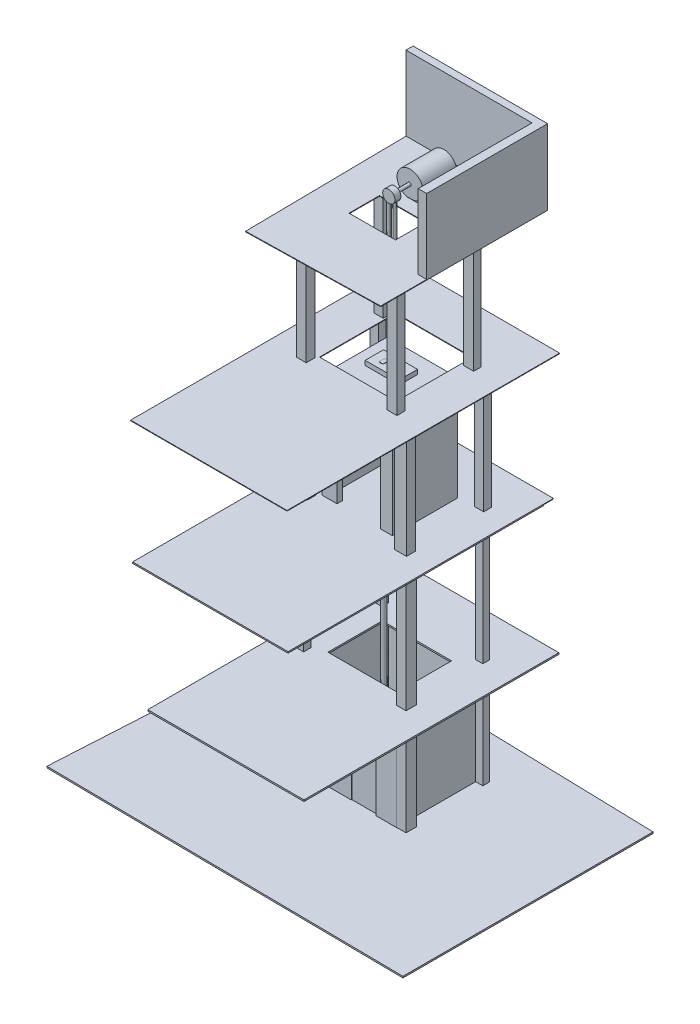
SolidWorks part; units mm, degrees
ref_plane "Front Plane" through (0, 0, 0) normal (0, 0, 1) x (1, 0, 0)
ref_plane "Top Plane" through (0, 0, 0) normal (0, 1, 0) x (1, 0, 0)
ref_plane "Right Plane" through (0, 0, 0) normal (1, 0, 0) x (0, 0, -1)
sketch "Sketch1" plane through (0, 0, 0) normal (0, 1, 0) x (1, 0, 0)
  line L1 (-1119.5185, 584.2256) -> (1199.1194, 522.7665)
  line L2 (-1119.5185, 584.2256) -> (-1218.0451, -1131.0237)
  line L3 (-1218.0451, -1131.0237) -> (1199.1194, -1157.1766)
  line L4 (1199.1194, 522.7665) -> (1199.1194, -1157.1766)
  line L5 (-1119.5185, 584.2256) -> (1199.1194, -1157.1766) construction
  line L6 (-1218.0451, -1131.0237) -> (1199.1194, 522.7665) construction
  point P0 (0, 0)
extrude "Boss-Extrude1" add sketch "Sketch1" along normal blind 10
sketch "Sketch2" plane through (0, 10, 0) normal (0, 1, 0) x (1, 0, 0)
  line L1 (-310.9875, 262.3228) -> (311.3377, 262.3228)
  line L2 (-310.9875, 262.3228) -> (-310.9875, -313.9536)
  line L3 (-310.9875, -313.9536) -> (311.3377, -313.9536)
  line L4 (311.3377, 262.3228) -> (311.3377, -313.9536)
  line L5 (-272.0145, 218.0111) -> (278.8911, 218.0111)
  line L6 (-272.0145, 218.0111) -> (-272.0145, -277.642)
  line L7 (-272.0145, -277.642) -> (278.8911, -277.642)
  line L8 (278.8911, 218.0111) -> (278.8911, -277.642)
extrude "Boss-Extrude2" add sketch "Sketch2" along normal blind 700
sketch "Sketch3" plane through (0, 710, 0) normal (0, 1, 0) x (1, 0, 0)
  line L1 (-498.5759, 538.5603) -> (550.6847, 538.5603)
  line L2 (-498.5759, 538.5603) -> (-498.5759, -1173.1855)
  line L3 (-498.5759, -1173.1855) -> (550.6847, -1173.441)
  line L4 (550.6847, 538.5603) -> (550.6847, -1173.441)
extrude "Boss-Extrude3" add sketch "Sketch3" along normal blind 10
sketch "Sketch4" plane through (0, 0, 313.9536) normal (0, 0, 1) x (1, 0, 0)
  line L1 (-169.9016, 641.4575) -> (173.8441, 641.4575)
  line L2 (-169.9016, 641.4575) -> (-169.9016, 10)
  line L3 (-169.9016, 10) -> (173.8441, 10)
  line L4 (173.8441, 641.4575) -> (173.8441, 10)
extrude "Cut-Extrude1" cut sketch "Sketch4" against normal blind 40
sketch "Sketch5" plane through (0, 0, 313.9536) normal (0, 0, 1) x (1, 0, 0)
  line L1 (-283.6713, 474.5331) -> (-187.5856, 474.5331)
  line L2 (-283.6713, 474.5331) -> (-283.6713, 265.4455)
  line L3 (-283.6713, 265.4455) -> (-187.5856, 265.4455)
  line L4 (-187.5856, 474.5331) -> (-187.5856, 265.4455)
extrude "Boss-Extrude4" add sketch "Sketch5" along normal blind 1
sketch "Sketch6" plane through (0, 0, 314.9536) normal (0, 0, 1) x (1, 0, 0)
  line L1 (-271.1746, 418.75) -> (-195.647, 418.75)
  line L2 (-271.1746, 418.75) -> (-271.1746, 375.0617)
  line L3 (-271.1746, 375.0617) -> (-195.647, 375.0617)
  line L4 (-195.647, 418.75) -> (-195.647, 375.0617)
extrude "Cut-Extrude2" cut sketch "Sketch6" against normal blind 1
sketch "Sketch7" plane through (0, 0, 314.9536) normal (0, 0, 1) x (1, 0, 0)
  circle A0 centre (-236.0757, 343.6172) radius 20.2971
  circle A1 centre (-236.0757, 291.5015) radius 20.232
extrude "Boss-Extrude5" add sketch "Sketch7" along normal blind 1
sketch "Sketch8" plane through (0, 0, 315.9536) normal (0, 0, 1) x (1, 0, 0)
  line L0 (-248.1005, 334.3432) -> (-224.1168, 334.3432)
  line L1 (-224.1168, 334.3432) -> (-236.1087, 356.5701)
  line L2 (-236.1087, 356.5701) -> (-248.1005, 334.3432)
  line L3 (-248.1005, 300.7341) -> (-224.1168, 300.7341)
  line L4 (-224.1168, 300.7341) -> (-236.1087, 278.0211)
  line L5 (-236.1087, 278.0211) -> (-248.1005, 300.7341)
extrude "Boss-Extrude6" add sketch "Sketch8" along normal blind 1
sketch "Sketch9" plane through (-169.9016, 0, 0) normal (1, 0, 0) x (0, 0, -1)
  line L1 (-304.9322, 641.4575) -> (-277.642, 641.4575)
  line L2 (-304.9322, 641.4575) -> (-304.9322, 10)
  line L3 (-304.9322, 10) -> (-277.642, 10)
  line L4 (-277.642, 641.4575) -> (-277.642, 10)
extrude "Boss-Extrude7" add sketch "Sketch9" along normal blind 170
sketch "Sketch10" plane through (0.0984, 0, 0) normal (1, 0, 0) x (0, 0, -1)
  line L1 (-301.4683, 640.5034) -> (-277.642, 640.5034)
  line L2 (-301.4683, 640.5034) -> (-301.4683, 10)
  line L3 (-301.4683, 10) -> (-277.642, 10)
  line L4 (-277.642, 640.5034) -> (-277.642, 10)
extrude "Boss-Extrude8" add sketch "Sketch10" along normal blind 170
sketch "Sketch11" plane through (0, 0, 313.9536) normal (0, 0, 1) x (1, 0, 0)
  line L1 (-53.7077, 693.9278) -> (48.7244, 693.9278)
  line L2 (-53.7077, 693.9278) -> (-53.7077, 651.2448)
  line L3 (-53.7077, 651.2448) -> (48.7244, 651.2448)
  line L4 (48.7244, 693.9278) -> (48.7244, 651.2448)
extrude "Boss-Extrude9" add sketch "Sketch11" along normal blind 1
sketch "Sketch12" plane through (0, 0, 314.9536) normal (0, 0, 1) x (1, 0, 0)
  line L1 (-47.5467, 689.1219) -> (41.8868, 689.1219)
  line L2 (-47.5467, 689.1219) -> (-47.5467, 655.2159)
  line L3 (-47.5467, 655.2159) -> (41.8868, 655.2159)
  line L4 (41.8868, 689.1219) -> (41.8868, 655.2159)
extrude "Cut-Extrude3" cut sketch "Sketch12" against normal blind 1
sketch "Sketch13" plane through (0, 0, 313.9536) normal (0, 0, 1) x (1, 0, 0)
  line L0 (-16.1887, 682.3335) -> (-12.3636, 682.3335)
  line L1 (-12.3636, 682.3335) -> (-16.2809, 666.1802)
  line L2 (-16.2809, 666.1802) -> (-10.8261, 666.1802)
  line L3 (-5.3714, 666.1802) -> (-5.3714, 662.7972)
  line L4 (-5.3714, 662.7972) -> (-7.9099, 662.7972)
  line L5 (-21.2894, 662.7972) -> (-16.1887, 682.3335)
  line L6 (-10.8261, 671.5233) -> (-10.8261, 666.1802)
  line L7 (-10.8261, 659.937) -> (-7.9099, 659.937)
  line L8 (-7.9099, 659.937) -> (-7.9099, 662.7972)
  line L9 (-7.9099, 671.5233) -> (-10.8261, 671.5233)
  line L10 (-10.8261, 662.7972) -> (-10.8261, 659.937)
  line L11 (-7.9099, 666.1802) -> (-5.3714, 666.1802)
  line L12 (-7.9099, 666.1802) -> (-7.9099, 671.5233)
  line L13 (-10.8261, 662.7972) -> (-21.2894, 662.7972)
extrude "Boss-Extrude10" add sketch "Sketch13" along normal blind 1
sketch "Sketch14" plane through (0, 0, 313.9536) normal (0, 0, 1) x (1, 0, 0)
  line L0 (8.2825, 678.5261) -> (25.4536, 678.5261)
  line L1 (25.4536, 678.5261) -> (16.868, 660.4022)
  line L2 (16.868, 660.4022) -> (8.2825, 678.5261)
extrude "Boss-Extrude11" add sketch "Sketch14" along normal blind 1
sketch "Sketch15" plane through (0, 0, 313.9536) normal (0, 0, 1) x (1, 0, 0)
  line L0 (-253.3924, 406.4083) -> (-253.3924, 387.5651)
  line L1 (-253.3924, 387.5651) -> (-258.9323, 387.5651)
  line L2 (-258.9323, 387.5651) -> (-258.9323, 385.0304)
  line L3 (-258.9323, 385.0304) -> (-244.3761, 385.0304)
  line L4 (-244.3761, 385.0304) -> (-244.3761, 387.5681)
  line L5 (-244.3761, 387.5681) -> (-249.8802, 387.5681)
  line L6 (-249.8802, 387.5681) -> (-249.8802, 410.5631)
  line L7 (-249.8802, 410.5631) -> (-259.6929, 410.2522)
  line L8 (-259.6929, 410.2522) -> (-259.5666, 406.4083)
  line L9 (-259.5666, 406.4083) -> (-253.3924, 406.4083)
extrude "Boss-Extrude12" add sketch "Sketch15" along normal blind 1
sketch "Sketch16" plane through (0, 0, 313.9536) normal (0, 0, 1) x (1, 0, 0)
  line L0 (-235.6485, 408.4658) -> (-235.6485, 385.5858)
  line L1 (-235.6485, 385.5858) -> (-232.1063, 385.5858)
  line L2 (-232.1063, 385.5858) -> (-232.2231, 401.9914)
  line L3 (-235.6485, 408.4658) -> (-231.8951, 408.4658)
  line L4 (-231.8951, 408.4658) -> (-231.8951, 406.5499)
  line L5 (-221.9834, 403.0568) -> (-221.9834, 385.5858)
  line L6 (-221.9834, 385.5858) -> (-218.8212, 385.5858)
  line L7 (-218.8212, 385.5858) -> (-219.0863, 397.9701)
  line L8 (-208.8863, 401.5917) -> (-208.8863, 385.5858)
  line L9 (-208.8863, 385.5858) -> (-206.271, 385.5858)
  line L10 (-206.271, 385.5858) -> (-206.5126, 401.9271)
  line L11 (-219.2828, 403.1887) -> (-219.0863, 397.9701)
  arc A4 (-221.9834, 403.0568) -> (-232.2231, 401.9914) centre (-226.8379, 399.9737) ccw
  arc A6 (-208.8863, 401.5917) -> (-219.2828, 403.1887) centre (-214.4049, 400.3049) ccw
  arc A7 (-206.5126, 401.9271) -> (-220.6047, 405.4509) centre (-214.4049, 400.3049) ccw
  arc A8 (-220.6047, 405.4509) -> (-231.8951, 406.6078) centre (-226.8379, 400.2912) ccw
  line M5 (-271.1746, 418.75) -> (-271.1746, 375.0617)
  line M6 (-271.1746, 375.0617) -> (-195.647, 375.0617)
  line M7 (-195.647, 375.0617) -> (-195.647, 418.75)
  line M8 (-195.647, 418.75) -> (-271.1746, 418.75)
  line M9 (-253.3924, 387.5651) -> (-253.3924, 406.4083)
  line M10 (-253.3924, 406.4083) -> (-259.5666, 406.4083)
  line M11 (-259.5666, 406.4083) -> (-259.6929, 410.2522)
  line M12 (-259.6929, 410.2522) -> (-249.8802, 410.5631)
  line M13 (-249.8802, 410.5631) -> (-249.8802, 387.5681)
  line M14 (-249.8802, 387.5681) -> (-244.3761, 387.5681)
  line M15 (-244.3761, 387.5681) -> (-244.3761, 385.0304)
  line M16 (-244.3761, 385.0304) -> (-258.9323, 385.0304)
  line M17 (-258.9323, 385.0304) -> (-258.9323, 387.5651)
  line M18 (-258.9323, 387.5651) -> (-253.3924, 387.5651)
extrude "Cut-Extrude4" cut sketch "Sketch16" against normal blind 2 contours A8 A7 L10 L9 L8 A6 L11 L7 L6 L5 A4 L2 L1 L0 L3 L4 M8 M5 M6 M7 M18 M9 M10 M11 M12 M13 M14 M15 M16 M17 region at (-233.4108, 417.8775, 313.9536)
sketch "Sketch17" plane through (0, 0, 311.9536) normal (0, 0, 1) x (1, 0, 0)
  line L1 (-271.2094, 458.8572) -> (-195.647, 458.8572)
  line L2 (-271.2094, 458.8572) -> (-271.2094, 418.4414)
  line L3 (-271.2094, 418.4414) -> (-195.7041, 418.4414)
  line L4 (-195.647, 458.8572) -> (-195.7041, 418.4414)
extrude "Cut-Extrude5" cut sketch "Sketch17" against normal blind 1
sketch "Sketch18" plane through (0, 0, 314.9536) normal (0, 0, 1) x (1, 0, 0)
  line L1 (-271.1417, 456.7599) -> (-195.647, 456.7599)
  line L2 (-271.1417, 456.7599) -> (-271.1417, 418.75)
  line L3 (-271.1417, 418.75) -> (-195.647, 418.75)
  line L4 (-195.647, 456.7599) -> (-195.647, 418.75)
extrude "Cut-Extrude6" cut sketch "Sketch18" against normal blind 3
sketch "Sketch19" plane through (0, 0, 310.9536) normal (0, 0, 1) x (1, 0, 0)
  line L0 (-254.3129, 446.7406) -> (-254.3129, 426.3557)
  line L1 (-254.3129, 426.3557) -> (-259.3962, 426.3557)
  line L2 (-259.3962, 426.3557) -> (-259.3962, 423.275)
  line L3 (-259.3962, 423.275) -> (-244.6783, 423.275)
  line L4 (-244.6783, 423.275) -> (-244.6783, 426.3453)
  line L5 (-244.6783, 426.3453) -> (-250.7281, 426.3453)
  line L6 (-250.7281, 426.3453) -> (-250.7281, 450.1154)
  line L7 (-250.7281, 450.1154) -> (-259.3962, 450.1154)
  line L8 (-259.3962, 450.1154) -> (-259.3962, 446.7406)
  line L9 (-259.3962, 446.7406) -> (-254.3129, 446.7406)
extrude "Boss-Extrude14" add sketch "Sketch19" along normal blind 2
sketch "Sketch20" plane through (0, 0, 310.9536) normal (0, 0, 1) x (1, 0, 0)
  line L0 (-231.7389, 449.8367) -> (-231.7389, 423.3615)
  line L1 (-231.7389, 423.3615) -> (-228.298, 423.3615)
  line L2 (-228.298, 423.3615) -> (-228.1456, 436.3278)
  line L3 (-231.7389, 449.8367) -> (-231.7389, 450.2937)
  line L4 (-231.7389, 450.2937) -> (-228.6156, 450.2937)
  line L5 (-228.6156, 450.2937) -> (-228.5661, 449.4447)
  line L6 (-228.5661, 446.4929) -> (-228.298, 439.2366)
  arc A0 (-228.1456, 436.3278) -> (-228.5661, 449.4447) centre (-224.524, 443.0091) ccw
  arc A1 (-228.298, 439.2366) -> (-228.5661, 446.4929) centre (-224.524, 443.0091) ccw
extrude "Boss-Extrude15" add sketch "Sketch20" along normal blind 2
sketch "Sketch21" plane through (0, 10, 0) normal (0, 1, 0) x (1, 0, 0)
  line L1 (-370.2495, 258.4828) -> (-312.2078, 258.4828)
  line L2 (-370.2495, 258.4828) -> (-370.2495, 212.8366)
  line L3 (-370.2495, 212.8366) -> (-312.2078, 212.8366)
  line L4 (-312.2078, 258.4828) -> (-312.2078, 212.8366)
  line L5 (-365.6413, -265.0657) -> (-310.9875, -265.0657)
  line L6 (-365.6413, -265.0657) -> (-365.6413, -313.9536)
  line L7 (-365.6413, -313.9536) -> (-310.9875, -313.9536)
  line L8 (-310.9875, -265.0657) -> (-310.9875, -313.9536)
  line L9 (311.5366, -242.3922) -> (375.3624, -242.3922)
  line L10 (311.5366, -242.3922) -> (311.5366, -312.5459)
  line L11 (311.5366, -312.5459) -> (375.3624, -312.5459)
  line L12 (375.3624, -242.3922) -> (375.3624, -312.5459)
  line L13 (311.3377, 262.3228) -> (359.7161, 262.3228)
  line L14 (311.3377, 262.3228) -> (311.3377, 218.7516)
  line L15 (311.3377, 218.7516) -> (359.7161, 218.7516)
  line L16 (359.7161, 262.3228) -> (359.7161, 218.7516)
extrude "Boss-Extrude16" add sketch "Sketch21" along normal blind 1600
sketch "Sketch22" plane through (0, 720, 0) normal (0, 1, 0) x (1, 0, 0)
  line L1 (-227.8036, 130.7691) -> (237.8382, 130.7691)
  line L2 (-227.8036, 130.7691) -> (-227.8036, -233.8627)
  line L3 (-227.8036, -233.8627) -> (237.8382, -233.8627)
  line L4 (237.8382, 130.7691) -> (237.8382, -233.8627)
extrude "Cut-Extrude7" cut sketch "Sketch22" against normal blind 70
sketch "Sketch23" plane through (0, 1610, 0) normal (0, 1, 0) x (1, 0, 0)
  line L1 (-509.8769, 452.1824) -> (534.1888, 452.1824)
  line L2 (-509.8769, 452.1824) -> (-509.8769, -1263.8932)
  line L3 (-509.8769, -1263.8932) -> (534.1888, -1263.8932)
  line L4 (534.1888, 452.1824) -> (534.1888, -1263.8932)
extrude "Boss-Extrude18" add sketch "Sketch23" along normal blind 5
sketch "Sketch24" plane through (0, 1615, 0) normal (0, 1, 0) x (1, 0, 0)
  line L1 (-262.9358, 199.4466) -> (209.8357, 199.4466)
  line L2 (-262.9358, 199.4466) -> (-262.9358, -239.2818)
  line L3 (-262.9358, -239.2818) -> (209.8357, -239.2818)
  line L4 (209.8357, 199.4466) -> (209.8357, -239.2818)
  line L5 (-236.9704, 157.98) -> (167.3482, 157.98)
  line L6 (-236.9704, 157.98) -> (-236.9704, -203.9085)
  line L7 (-236.9704, -203.9085) -> (167.3482, -203.9085)
  line L8 (167.3482, 157.98) -> (167.3482, -203.9085)
extrude "Boss-Extrude19" add sketch "Sketch24" along normal blind 700
sketch "Sketch25" plane through (0, 0, 239.2818) normal (0, 0, 1) x (1, 0, 0)
  line L1 (-161.3526, 2253.91) -> (128.896, 2253.91)
  line L2 (-161.3526, 2253.91) -> (-161.3526, 1615)
  line L3 (-161.3526, 1615) -> (128.896, 1615)
  line L4 (128.896, 2253.91) -> (128.896, 1615)
extrude "Cut-Extrude8" cut sketch "Sketch25" against normal blind 40
sketch "Sketch26" plane through (0, 1615, 0) normal (0, 1, 0) x (1, 0, 0)
  line L1 (-392.0328, 260.8249) -> (-332.3431, 260.8249)
  line L2 (-392.0328, 260.8249) -> (-392.0328, 211.3493)
  line L3 (-392.0328, 211.3493) -> (-332.3431, 211.3493)
  line L4 (-332.3431, 260.8249) -> (-332.3431, 211.3493)
  line L5 (-362.188, -262.1021) -> (-282.7219, -262.1021)
  line L6 (-362.188, -262.1021) -> (-362.188, -314.4144)
  line L7 (-362.188, -314.4144) -> (-282.7219, -314.4144)
  line L8 (-282.7219, -262.1021) -> (-282.7219, -314.4144)
  line L9 (317.4199, 260.5296) -> (377.7458, 260.5296)
  line L10 (317.4199, 260.5296) -> (317.4199, 206.3146)
  line L11 (317.4199, 206.3146) -> (377.7458, 206.3146)
  line L12 (377.7458, 260.5296) -> (377.7458, 206.3146)
  line L13 (296.7901, -252.3262) -> (377.7458, -252.3262)
  line L14 (296.7901, -252.3262) -> (296.7901, -312.0443)
  line L15 (296.7901, -312.0443) -> (377.7458, -312.0443)
  line L16 (377.7458, -252.3262) -> (377.7458, -312.0443)
extrude "Boss-Extrude20" add sketch "Sketch26" along normal blind 800
sketch "Sketch28" plane through (0, 2315, 0) normal (0, 1, 0) x (1, 0, 0)
  line L1 (209.7663, 199.4466) -> (-262.9063, 199.4466)
  line L2 (209.7663, 199.4466) -> (209.7663, -239.2818)
  line L3 (209.7663, -239.2818) -> (-262.9063, -239.2818)
  line L4 (-262.9063, 199.4466) -> (-262.9063, -239.2818)
extrude "Boss-Extrude21" add sketch "Sketch28" along normal blind 4
sketch "Sketch29" plane through (0, 2319, 0) normal (0, 1, 0) x (1, 0, 0)
  line L1 (57.1272, 82.8953) -> (-171.3197, 82.8953)
  line L2 (57.1272, 82.8953) -> (57.1272, -40.6557)
  line L3 (57.1272, -40.6557) -> (-171.3197, -40.6557)
  line L4 (-171.3197, 82.8953) -> (-171.3197, -40.6557)
extrude "Boss-Extrude22" add sketch "Sketch29" along normal blind 30
sketch "Sketch30" plane through (0, 1615, 0) normal (0, 1, 0) x (1, 0, 0)
  line L1 (534.1888, 518.807) -> (-509.8769, 518.807)
  line L2 (534.1888, 518.807) -> (534.1888, -1263.8932)
  line L3 (534.1888, -1263.8932) -> (-509.8769, -1263.8932)
  line L4 (-509.8769, 518.807) -> (-509.8769, -1263.8932)
extrude "Boss-Extrude23" add sketch "Sketch30" along normal blind 4
sketch "Sketch31" plane through (0, 2415, 0) normal (0, 1, 0) x (1, 0, 0)
  line L1 (509.5029, 584.8272) -> (-541.0801, 584.8272)
  line L2 (509.5029, 584.8272) -> (509.5029, -1245.8933)
  line L3 (509.5029, -1245.8933) -> (-541.0801, -1245.8933)
  line L4 (-541.0801, 584.8272) -> (-541.0801, -1245.8933)
extrude "Boss-Extrude24" add sketch "Sketch31" along normal blind 4
sketch "Sketch32" plane through (0, 2419, 0) normal (0, 1, 0) x (1, 0, 0)
  line L1 (-273.2763, 267.1919) -> (241.7138, 267.1919)
  line L2 (-273.2763, 267.1919) -> (-273.2763, -244.6131)
  line L3 (-273.2763, -244.6131) -> (241.7138, -244.6131)
  line L4 (241.7138, 267.1919) -> (241.7138, -244.6131)
extrude "Cut-Extrude9" cut sketch "Sketch32" against normal blind 4
sketch "Sketch33" plane through (0, 2419, 0) normal (0, 1, 0) x (1, 0, 0)
  line L1 (-348.3927, 194.6348) -> (-285.0254, 194.6348)
  line L2 (-348.3927, 194.6348) -> (-348.3927, 250.7404)
  line L3 (-348.3927, 250.7404) -> (-285.0254, 250.7404)
  line L4 (-285.0254, 194.6348) -> (-285.0254, 250.7404)
  line L5 (-348.3927, -322.8817) -> (-285.0254, -322.8817)
  line L6 (-348.3927, -322.8817) -> (-348.3927, -262.5669)
  line L7 (-348.3927, -262.5669) -> (-285.0254, -262.5669)
  line L8 (-285.0254, -322.8817) -> (-285.0254, -262.5669)
  line L9 (260.001, -324.9173) -> (326.8178, -324.9173)
  line L10 (260.001, -324.9173) -> (260.001, -272.0698)
  line L11 (260.001, -272.0698) -> (326.8178, -272.0698)
  line L12 (326.8178, -324.9173) -> (326.8178, -272.0698)
  line L13 (260.001, 190.1754) -> (326.8178, 190.1754)
  line L14 (260.001, 190.1754) -> (260.001, 238.0831)
  line L15 (260.001, 238.0831) -> (326.8178, 238.0831)
  line L16 (326.8178, 190.1754) -> (326.8178, 238.0831)
extrude "Boss-Extrude25" add sketch "Sketch33" along normal blind 800
sketch "Sketch34" plane through (0, 3219, 0) normal (0, 1, 0) x (1, 0, 0)
  line L1 (438.8935, 574.7386) -> (-464.6289, 574.7386)
  line L2 (438.8935, 574.7386) -> (438.8935, -546.4396)
  line L3 (438.8935, -546.4396) -> (-449.6246, -565.2649)
  line L4 (-464.6289, 574.7386) -> (-449.6246, -565.2649)
  line L5 (104.6135, 91.9277) -> (-207.4731, 91.9277)
  line L6 (104.6135, 91.9277) -> (104.6135, -112.4976)
  line L7 (104.6135, -112.4976) -> (-207.4731, -112.4976)
  line L8 (-207.4731, 91.9277) -> (-207.4731, -112.4976)
extrude "Boss-Extrude26" add sketch "Sketch34" along normal blind 4
sketch "Sketch35" plane through (0, 3223, 0) normal (0, 1, 0) x (1, 0, 0)
  line L1 (-111.9386, 304.9138) -> (0, 304.9138)
  line L2 (-111.9386, 304.9138) -> (-111.9386, 177.0343)
  line L3 (-111.9386, 177.0343) -> (0, 177.0343)
  line L4 (0, 304.9138) -> (0, 177.0343)
extrude "Boss-Extrude27" add sketch "Sketch35" along normal blind 30
sketch "Sketch36" plane through (0, 3253, 0) normal (0, 1, 0) x (1, 0, 0)
  line L1 (-197.8726, 375.6473) -> (81.8348, 375.6473)
  line L2 (-197.8726, 375.6473) -> (-197.8726, 148.2555)
  line L3 (-197.8726, 148.2555) -> (81.8348, 148.2555)
  line L4 (81.8348, 375.6473) -> (81.8348, 148.2555)
extrude "Boss-Extrude28" add sketch "Sketch36" along normal blind 200
sketch "Sketch37" plane through (0, 0, -148.2555) normal (0, 0, 1) x (1, 0, 0)
  line L0 (-36.5137, 3251.8374) -> (81.8348, 3251.4916)
  line L1 (-197.8726, 3453) -> (81.8348, 3453)
  line L2 (-197.8726, 3453) -> (-197.8726, 3252.3089)
  line L3 (-197.8726, 3252.3089) -> (-80.9439, 3251.9672)
  line L4 (81.8348, 3453) -> (81.8348, 3251.4916)
  arc A0 (-36.5137, 3251.8374) -> (-80.9439, 3251.9672) centre (-58.4819, 3336.3791) ccw
extrude "Cut-Extrude12" cut sketch "Sketch37" against normal blind 300
sketch "Sketch38" plane through (0, 3223, 0) normal (0, 1, 0) x (1, 0, 0)
  line L1 (82.3765, 437.8048) -> (200.0694, 437.8048)
  line L2 (82.3765, 437.8048) -> (82.3765, 146.1268)
  line L3 (82.3765, 146.1268) -> (200.0694, 146.1268)
  line L4 (200.0694, 437.8048) -> (200.0694, 146.1268)
extrude "Boss-Extrude30" add sketch "Sketch38" along normal blind 100
sketch "Sketch39" plane through (0, 0, -148.2555) normal (0, 0, 1) x (1, 0, 0)
  circle A0 centre (-61.6258, 3334.5719) radius 10.8281
extrude "Boss-Extrude31" add sketch "Sketch39" along normal blind 100
sketch "Sketch40" plane through (0, 0, -48.2555) normal (0, 0, 1) x (1, 0, 0)
  circle A0 centre (-61.2375, 3333.5153) radius 41.0186
extrude "Boss-Extrude32" add sketch "Sketch40" along normal blind 40
sketch "Sketch41" plane through (0, 2349, 0) normal (0, 1, 0) x (1, 0, 0)
  line L1 (-115.5151, 33.8271) -> (-88.069, 33.8271)
  line L2 (-115.5151, 33.8271) -> (-115.5151, -3.9297)
  line L3 (-115.5151, -3.9297) -> (-88.069, -3.9297)
  line L4 (-88.069, 33.8271) -> (-88.069, -3.9297)
  line L5 (-3.1738, 33.8271) -> (21.6081, 33.8271)
  line L6 (-3.1738, 33.8271) -> (-3.1738, -3.9297)
  line L7 (-3.1738, -3.9297) -> (21.6081, -3.9297)
  line L8 (21.6081, 33.8271) -> (21.6081, -3.9297)
extrude "Boss-Extrude33" add sketch "Sketch41" along normal blind 2
sketch "Sketch44" plane through (0, 2349, 0) normal (0, 1, 0) x (1, 0, 0)
  circle A0 centre (-69.8187, 25.1407) radius 11.4671
sketch3d "3DSketch3"
  line L0 (-69.8187, 2349, -25.1407) -> (-79.1852, 3344.6746, -25.1407)
sweep "Sweep2" add profiles "Sketch44" path "3DSketch3"
sketch "Sketch46" plane through (0, 2349, 0) normal (0, 1, 0) x (1, 0, 0)
  circle A0 centre (-25.0699, 26.1332) radius 9.8236
sketch3d "3DSketch5"
  line L0 (-25.0699, 2349, -26.1332) -> (-39.6492, 3323.4674, -26.1332)
sweep "Sweep3" add profiles "Sketch46" path "3DSketch5"
sketch "Sketch47" plane through (0, 0, 0) normal (0, -1, 0) x (-1, 0, 0)
  line L1 (307.844, -399.3506) -> (-315.4623, -399.3506)
  line L2 (307.844, -399.3506) -> (307.844, 171.3279)
  line L3 (307.844, 171.3279) -> (-315.4623, 171.3279)
  line L4 (-315.4623, -399.3506) -> (-315.4623, 171.3279)
  line L5 (284.1002, -349.204) -> (-265.7287, -349.204)
  line L6 (284.1002, -349.204) -> (284.1002, 113.2378)
  line L7 (284.1002, 113.2378) -> (-265.7287, 113.2378)
  line L8 (-265.7287, -349.204) -> (-265.7287, 113.2378)
extrude "Boss-Extrude34" add sketch "Sketch47" along normal blind 300
sketch "Sketch48" plane through (0, 0, 399.3506) normal (0, 0, 1) x (1, 0, 0)
  line L1 (-252.9384, -33.6607) -> (262.0186, -33.6607)
  line L2 (-252.9384, -33.6607) -> (-252.9384, -300)
  line L3 (-252.9384, -300) -> (262.0186, -300)
  line L4 (262.0186, -33.6607) -> (262.0186, -300)
extrude "Cut-Extrude13" cut sketch "Sketch48" against normal blind 60
sketch "Sketch49" plane through (0, -300, 0) normal (0, -1, 0) x (-1, 0, 0)
  line L1 (307.3968, -399.3647) -> (-315.4623, -399.3647)
  line L2 (307.3968, -399.3647) -> (307.3968, 171.3279)
  line L3 (307.3968, 171.3279) -> (-315.4623, 171.3279)
  line L4 (-315.4623, -399.3647) -> (-315.4623, 171.3279)
extrude "Boss-Extrude35" add sketch "Sketch49" along normal blind 70
sketch "Sketch50" plane through (0, -300, 0) normal (0, 1, 0) x (1, 0, 0)
  line L1 (-102.7746, 45.6614) -> (93.5859, 45.6614)
  line L2 (-102.7746, 45.6614) -> (-102.7746, -223.6374)
  line L3 (-102.7746, -223.6374) -> (93.5859, -223.6374)
  line L4 (93.5859, 45.6614) -> (93.5859, -223.6374)
extrude "Boss-Extrude36" add sketch "Sketch50" along normal blind 50
sketch "Sketch51" plane through (0, 0, 399.3647) normal (0, 0, 1) x (1, 0, 0)
  line L0 (-299.7141, -334.8216) -> (-514.6921, -498.8959)
  line L1 (-514.6921, -498.8959) -> (537.0814, -490.3229)
  line L2 (537.0814, -490.3229) -> (286.7213, -326.1397)
  line L3 (286.7213, -326.1397) -> (-299.7141, -334.8216)
extrude "Boss-Extrude37" add sketch "Sketch51" against normal blind 800
sketch "Sketch52" plane through (0, -250, 0) normal (0, 1, 0) x (1, 0, 0)
  circle A0 centre (-12.1566, -71.2779) radius 16.0984
sketch3d "3DSketch7"
  line L0 (-12.1566, -250, 71.2779) -> (-18.0957, 1594.4509, 71.2779)
sweep "Sweep5" add profiles "Sketch52" path "3DSketch7"
sketch "Sketch53" plane through (0, 3223, 0) normal (0, 1, 0) x (1, 0, 0)
  line L1 (-464.6289, 574.7386) -> (438.8935, 574.7386)
  line L2 (-464.6289, 574.7386) -> (-464.6289, 527.0292)
  line L3 (-464.6289, 527.0292) -> (382.186, 527.0292)
  line L4 (438.8935, 574.7386) -> (438.8935, 527.0292)
  line L5 (382.186, 574.7386) -> (438.8935, 574.7386)
  line L6 (382.186, 527.0292) -> (382.186, -237.4718)
  line L7 (382.186, -237.4718) -> (438.8935, -237.4718)
  line L8 (438.8935, 574.7386) -> (438.8935, -237.4718)
extrude "Boss-Extrude38" add sketch "Sketch53" along normal blind 500 contours L8 L7 L6 L3 L2 L1
